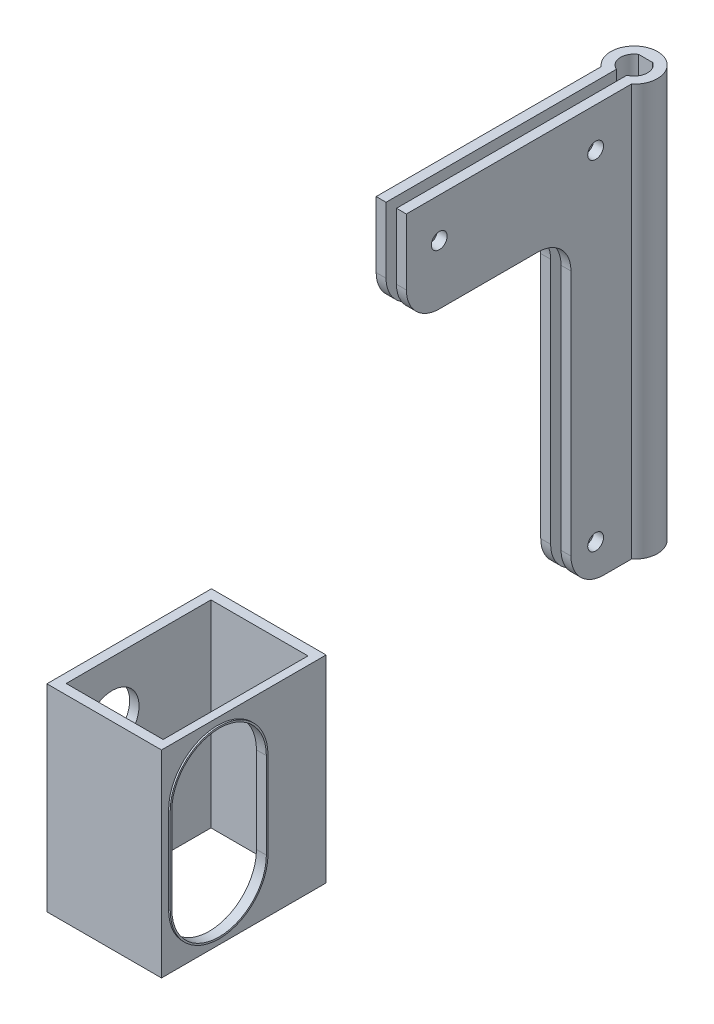
SolidWorks part; units mm, degrees
ref_plane "Front Plane" through (0, 0, 0) normal (0, 0, 1) x (1, 0, 0)
ref_plane "Top Plane" through (0, 0, 0) normal (0, 1, 0) x (1, 0, 0)
ref_plane "Right Plane" through (0, 0, 0) normal (1, 0, 0) x (0, 0, -1)
ref_plane "ULTRASONIC CENTER" through (0, 0, 125) normal (0, 0, 1) x (1, 0, 0)
sketch "Sketch1" plane through (0, 0, 0) normal (0, 1, 0) x (1, 0, 0)
  line L0 (-1.5875, -3.7802) -> (-1.5875, -23.7802)
  line L1 (1.5875, -3.7802) -> (1.5875, -23.7802)
  line L2 (2.1354, 3.5) -> (-2.1354, 3.5)
  line L3 (4.5875, -5.4189) -> (4.5875, -23.7802)
  line L4 (-4.5875, -5.4189) -> (-4.5875, -23.7802)
  line L5 (-4.5875, -23.7802) -> (-1.5875, -23.7802)
  line L6 (1.5875, -23.7802) -> (4.5875, -23.7802)
  arc A0 (1.5875, -3.7802) -> (2.1354, 3.5) centre (0, 0) ccw
  arc A1 (4.5875, -5.4189) -> (-4.5875, -5.4189) centre (0, 0) ccw
  arc A2 (-2.1354, 3.5) -> (-1.5875, -3.7802) centre (0, 0) ccw
  arc A4 (1.5875, -3.7802) -> (-1.5875, -3.7802) centre (0, 0) ccw construction
  dimension "D1" = 4.1
  dimension "D2" = 20
  dimension "D3" = 3.5
  dimension "D5" = 3.175
  dimension "D4" = 3
extrude "Boss-Extrude1" add sketch "Sketch1" along normal blind 125
ref_plane "PADDLE CENTER" through (0, 0, 0) normal (-1, 0, 0) x (0, 0, 1)
ref_plane "DISC CENTER" through (0, -15, 0) normal (0, 1, 0) x (1, 0, 0)
ref_axis "Axis1" through (0, -15, 24.7802) along (0, 0, -1)
ref_plane "OFFSET" through (-36.4125, 0, 0) normal (-1, 0, 0) x (0, 0, 1)
ref_plane "PADDLE SURFACE" through (-1.5875, 0, 0) normal (1, 0, 0) x (0, 0, -1)
ref_axis "Axis2" through (-36.4125, -15, -8.644) along (0, 0, 1)
ref_point "ULTRASONIC"
sketch "Sketch5" plane through (0, 125, 0) normal (0, 1, 0) x (1, 0, 0)
  line L1 (-1.5875, -111.6) -> (-1.5875, -106.6)
  line L2 (-47.5875, -106.6) -> (-47.5875, -141.6)
  line L3 (-47.5875, -141.6) -> (-1.5875, -141.6)
  line L4 (-1.5875, -141.6) -> (-1.5875, -136.6)
  line L5 (-1.5875, -136.6) -> (-42.5875, -136.6)
  line L9 (-1.5875, -23.7802) -> (-1.5875, -3.7802) construction
  line L10 (-42.5875, -111.6) -> (-1.5875, -111.6)
  line L12 (-42.5875, -136.6) -> (-42.5875, -111.6)
  line L13 (-47.5875, -106.6) -> (-1.5875, -106.6)
  line L18 (-18.6703, -4.1) -> (17.7565, -4.1) construction
  circle A0 centre (0, 0) radius 4.1 construction
  arc A1 (-2.1354, 3.5) -> (-1.5875, -3.7802) centre (0, 0) ccw construction
  point P2 (-42.5875, -124.1)
  dimension "D2" = 120
  dimension "D1" = 41
  dimension "D3" = 25
  dimension "D4" = 5
  dimension "D5" = 5
  dimension "D7" = 5
extrude "Boss-Extrude2" [suppressed] add sketch "Sketch5" against normal mid plane 30 from offset 137.5 offset against normal yes
sketch "Sketch6" plane through (0, 125, 0) normal (0, 1, 0) x (1, 0, 0)
  line L0 (4.5875, -23.7802) -> (4.5875, -5.4189) construction
  line L1 (1.5875, -23.7802) -> (4.5875, -23.7802)
  line L2 (1.5875, -23.7802) -> (1.5875, -73.7802)
  line L3 (1.5875, -73.7802) -> (4.5875, -73.7802)
  line L4 (4.5875, -23.7802) -> (4.5875, -73.7802)
  line L6 (-1.5875, -23.7802) -> (-1.5875, -3.7802) construction
  line L7 (-4.5875, -23.7802) -> (-1.5875, -23.7802)
  line L8 (-4.5875, -23.7802) -> (-4.5875, -73.7802)
  line L9 (-4.5875, -73.7802) -> (-1.5875, -73.7802)
  line L10 (-1.5875, -23.7802) -> (-1.5875, -73.7802)
  dimension "D1" = 50
extrude "Boss-Extrude3" add sketch "Sketch6" against normal blind 30
fillet "Fillet6" radius 10 6 edges at (3.0875, 0, 23.7802) (-3.0875, 0, 23.7802) (3.0875, 95, 73.7802) (-3.0875, 95, 73.7802) (3.0875, 95, 23.7802) (-3.0875, 95, 23.7802)
hole_wizard "M4 Clearance Hole1" positions "Sketch2" profile "Sketch3" hole size "M4" standard "ANSI Metric" end condition through all
sketch "Sketch2" plane through (4.5875, 0, 0) normal (1, 0, 0) x (0, 0, -1)
  line L4 (-73.7802, 125) -> (-5.4189, 125) construction
  line L6 (-73.7802, 105) -> (-73.7802, 125) construction
  point P0 (-16.2802, 113)
  point P4 (-16.2802, 10)
  point P19 (-63.7802, 113)
  dimension "D1" = 103
  dimension "D2" = 12
  dimension "D3" = 47.5
  dimension "D4" = 10
sketch "Sketch3" plane through (4.5875, 113, 16.2802) normal (0, 1, 0) x (0, 0, -1)
  line L0 (0, 0) -> (0, 11.6875)
  line L1 (0, 11.6875) -> (2.4, 11.6875)
  line L2 (2.4, 11.6875) -> (2.4, 0)
  line L5 (2.4, 0) -> (0, 0)
  line L11 (0, -6.35) -> (0, 107.95) construction
  dimension "Thru Hole Dia." = 4.8
  dimension "Thru Hole Depth" = 11.6875
sketch "Sketch9" [suppressed] plane through (-1.5875, 0, 0) normal (1, 0, 0) x (0, 0, -1)
  line L0 (-105.675, 2.5) -> (-22.7496, 2.5)
  line L1 (-105.675, 2.5) -> (-105.675, -27.5)
  line L2 (-105.675, -27.5) -> (-22.7496, -27.5)
  line L3 (-22.7496, 95) -> (-22.7496, 0) construction
  line L5 (-4.1335, 0) -> (-4.1335, -27.5)
  line L6 (-4.1335, -27.5) -> (-22.7496, -27.5)
  line L7 (-22.7496, 2.5) -> (-22.7496, 0)
  line L8 (-22.7496, 95) -> (-22.7496, 0) construction
  line L9 (-22.7496, 0) -> (-4.1335, 0) construction
  line L10 (-22.7496, 0) -> (-4.1335, 0)
extrude "Boss-Extrude5" [suppressed] add sketch "Sketch9" against normal up to surface (3 mm away) up to face at (-4.5875, 113, 13.8802)
chamfer "Chamfer2" [suppressed] distance 42 distance2 35
fillet "Fillet1" [suppressed] radius 40
fillet "Fillet2" [suppressed] radius 10
sketch "Sketch11" plane through (0, 125, 0) normal (0, 1, 0) x (1, 0, 0)
  line L0 (-21.2191, -4.1) -> (29.064, -4.1) construction
  line L1 (4.5875, -66.6) -> (47.5875, -66.6)
  line L2 (4.5875, -73.7802) -> (4.5875, -5.4189) construction
  line L3 (47.5875, -66.6) -> (47.5875, -101.6)
  line L4 (47.5875, -101.6) -> (4.5875, -101.6)
  line L5 (4.5875, -101.6) -> (4.5875, -96.6)
  line L6 (4.5875, -96.6) -> (42.5875, -96.6)
  line L7 (42.5875, -96.6) -> (42.5875, -71.6)
  line L8 (42.5875, -71.6) -> (4.5875, -71.6)
  line L9 (4.5875, -71.6) -> (4.5875, -66.6)
  line L10 (1.5875, -3.7802) -> (1.5875, -73.7802) construction
  circle A0 centre (0, 0) radius 4.1 construction
  arc A1 (-2.1354, 3.5) -> (-1.5875, -3.7802) centre (0, 0) ccw construction
  point P17 (42.5875, -84.1)
  dimension "D1" = 5
  dimension "D2" = 5
  dimension "D3" = 5
  dimension "D4" = 41
  dimension "D5" = 80
  dimension "D6" = 25
extrude "Boss-Extrude6" [suppressed] add sketch "Sketch11" along normal mid plane 30 from offset 137.5 offset against normal yes
sketch "Sketch13" [suppressed] plane through (4.5875, 0, 0) normal (-1, 0, 0) x (0, 0, 1)
  line L0 (70.675, 2.5) -> (22.7496, 2.5)
  line L1 (22.7496, 55) -> (22.7496, 42.5) construction
  line L2 (22.7496, 2.5) -> (22.7496, 0)
  line L3 (22.7496, 0) -> (4.1335, 0)
  line L4 (70.675, 2.5) -> (70.675, -27.5)
  line L5 (70.675, -27.5) -> (4.1335, -27.5)
  line L6 (4.1335, -27.5) -> (4.1335, 0)
extrude "Boss-Extrude8" [suppressed] add sketch "Sketch13" along normal up to surface (3 mm away) up to face at (1.5875, 113, 13.8802)
chamfer "Chamfer3" [suppressed] distance 42 distance2 35
fillet "Fillet5" [suppressed] radius 40
fillet "Fillet4" [suppressed] radius 10
sketch "Sketch14" [suppressed] plane through (0, 0, 110.675) normal (0, 0, 1) x (1, 0, 0)
  line L5 (-47.5875, -27.5) -> (-47.5875, 2.5) construction
  line L6 (-40.0875, -7.5) -> (-40.0875, -17.5) construction
  line L7 (-37.5875, -7.5) -> (-37.5875, -17.5)
  line L8 (-42.5875, -7.5) -> (-42.5875, -17.5)
  line L9 (-42.5875, -27.5) -> (-42.5875, 2.5) construction
  arc A0 (-37.5875, -7.5) -> (-42.5875, -7.5) centre (-40.0875, -7.5) ccw
  arc A1 (-42.5875, -17.5) -> (-37.5875, -17.5) centre (-40.0875, -17.5) ccw
  point P2 (-40.0875, -12.5)
  point P9 (-47.5875, -12.5)
  dimension "D1" = 5
  dimension "D2" = 10
extrude "Cut-Extrude1" [suppressed] cut sketch "Sketch14" against normal up to next
sketch "Sketch15" [suppressed] plane through (0, 0, 70.675) normal (0, 0, 1) x (1, 0, 0)
  line L0 (40.0875, -7.5) -> (40.0875, -17.5) construction
  line L1 (42.5875, -7.5) -> (42.5875, -17.5)
  line L2 (37.5875, -7.5) -> (37.5875, -17.5)
  line L3 (42.5875, 2.5) -> (42.5875, -27.5) construction
  arc A0 (42.5875, -7.5) -> (37.5875, -7.5) centre (40.0875, -7.5) ccw
  arc A1 (37.5875, -17.5) -> (42.5875, -17.5) centre (40.0875, -17.5) ccw
  point P2 (40.0875, -12.5)
  point P9 (42.5875, -12.5)
  dimension "D1" = 5
  dimension "D2" = 10
extrude "Cut-Extrude2" [suppressed] cut sketch "Sketch15" against normal up to next
sketch "Sketch16" plane through (-36.4125, 0, 0) normal (-1, 0, 0) x (0, 0, 1)
  line L0 (125, 15) -> (125, -45) construction
  line L1 (92, 15) -> (142, 15)
  line L3 (92, -45) -> (142, -45)
  line L4 (142, 15) -> (142, -45)
  line L5 (92, 15) -> (142, -45) construction
  line L6 (92, -45) -> (142, 15) construction
  line L7 (132.5, -11) -> (132.5, -19) construction
  line L12 (92, 15) -> (92, -45)
  line L13 (134.75, -11) -> (134.75, -19)
  line L14 (130.25, -11) -> (130.25, -19)
  line L15 (116.35, -10) -> (116.35, -20) construction
  line L16 (117.35, -10) -> (117.35, -20)
  line L17 (115.35, -10) -> (115.35, -20)
  circle A0 centre (125, -2) radius 8.15
  circle A1 centre (125, -28) radius 8.15
  arc A4 (134.75, -11) -> (130.25, -11) centre (132.5, -11) ccw
  arc A5 (130.25, -19) -> (134.75, -19) centre (132.5, -19) ccw
  arc A6 (117.35, -10) -> (115.35, -10) centre (116.35, -10) ccw
  arc A7 (115.35, -20) -> (117.35, -20) centre (116.35, -20) ccw
  point P1 (117, -15)
  point P14 (125, -15)
  point P15 (132.5, -15)
  point P26 (116.35, -15)
  dimension "D4" = 16.3
  dimension "D5" = 16.3
  dimension "D1" = 60
  dimension "D3" = 50
  dimension "D6" = 26
  dimension "D7" = 13
  dimension "D2" = 17
  dimension "D8" = 7.5
  dimension "D10" = 4.5
  dimension "D11" = 8
  dimension "D12" = 8.65
  dimension "D13" = 2
  dimension "D14" = 10
extrude "Boss-Extrude9" add sketch "Sketch16" against normal blind 2.85 separate body contours L3 L4 L1 L12 A1 A0 region at (-36.4125, 14.219, 117)
sketch "Sketch19" plane through (-33.5625, 0, 0) normal (1, 0, 0) x (0, 0, -1)
  line L0 (-92, -45) -> (-142, -45) construction
  line L9 (-142, 15) -> (-139.5, 15)
  line L10 (-142, 15) -> (-142, -45)
  line L11 (-142, -45) -> (-139.5, -45)
  line L12 (-139.5, 15) -> (-139.5, -45)
  line L13 (-92, 15) -> (-142, 15) construction
  line L14 (-92, -45) -> (-94.5, -45)
  line L15 (-92, -45) -> (-92, 15)
  line L16 (-92, 15) -> (-94.5, 15)
  line L17 (-94.5, -45) -> (-94.5, 15)
  dimension "D1" = 2.5
  dimension "D2" = 2.5
extrude "Boss-Extrude11" add sketch "Sketch19" along normal up to surface (31.975 mm away) up to plane "PADDLE SURFACE"
sketch "Sketch20" plane through (0, -45, 0) normal (0, -1, 0) x (1, 0, 0)
  line L0 (-1.5875, 92) -> (-36.4125, 92) construction
  line L1 (-1.5875, 142) -> (-4.0875, 142)
  line L2 (-1.5875, 142) -> (-1.5875, 92)
  line L3 (-1.5875, 92) -> (-4.0875, 92)
  line L4 (-4.0875, 142) -> (-4.0875, 92)
  dimension "D1" = 2.5
extrude "Boss-Extrude12" add sketch "Sketch20" against normal up to surface (60 mm away) up to face at (-18.2875, 15, 117)
sketch "Sketch21" plane through (-1.5875, 0, 0) normal (1, 0, 0) x (0, 0, -1)
  line L0 (-125, -1.9) -> (-125, -28.1) construction
  line L1 (-125, 55) -> (-125, -55) construction
  line L2 (-110, -1.9) -> (-110, -28.1) construction
  line L3 (-140, -1.9) -> (-140, -28.1) construction
  line L4 (-110.15, -1.9) -> (-110.15, -28.1)
  line L5 (-139.85, -1.9) -> (-139.85, -28.1)
  line L6 (-110.65, -1.9) -> (-110.65, -28.1)
  line L7 (-139.35, -1.9) -> (-139.35, -28.1)
  arc A0 (-110, -1.9) -> (-140, -1.9) centre (-125, -1.9) ccw construction
  arc A1 (-140, -28.1) -> (-110, -28.1) centre (-125, -28.1) ccw construction
  arc A2 (-139.85, -28.1) -> (-110.15, -28.1) centre (-125, -28.1) ccw
  arc A3 (-110.15, -1.9) -> (-139.85, -1.9) centre (-125, -1.9) ccw
  arc A4 (-139.35, -28.1) -> (-110.65, -28.1) centre (-125, -28.1) ccw
  arc A5 (-110.65, -1.9) -> (-139.35, -1.9) centre (-125, -1.9) ccw
  point P5 (-125, -15)
  dimension "D1" = 26.2
  dimension "D2" = 30
  dimension "D3" = 0.15
  dimension "D4" = 0.5
extrude "Cut-Extrude3" cut sketch "Sketch21<2>" against normal up to next (2.5 mm away) contours L6 A5 L7 A4 region at (-1.5875, -15, 125)
sketch "Sketch21<2>" plane through (-1.5875, 0, 0) normal (1, 0, 0) x (0, 0, -1) same geometry as "Sketch21"
extrude "Boss-Extrude13" add sketch "Sketch21" along normal blind 0.5
sketch "Sketch18" plane through (0, -45, 0) normal (0, -1, 0) x (1, 0, 0)
  line L0 (-1.5875, -68.75) -> (-1.5875, 68.75) construction
  line L1 (-36.4125, 142) -> (-1.5875, 142)
  line L2 (-36.4125, 142) -> (-36.4125, 139)
  line L3 (-36.4125, 139) -> (-1.5875, 139)
  line L4 (-1.5875, 142) -> (-1.5875, 139)
  line L6 (-36.4125, 92) -> (-1.5875, 92)
  line L7 (-36.4125, 92) -> (-36.4125, 95)
  line L8 (-36.4125, 95) -> (-1.5875, 95)
  line L9 (-1.5875, 92) -> (-1.5875, 95)
  dimension "D1" = 3
  dimension "D2" = 3
extrude "Boss-Extrude10" add sketch "Sketch18" against normal up to surface (60 mm away) up to face at (-18.825, 15, 117)
equation "\"D7@Sketch16\"=\"D6@Sketch16\"/2"
